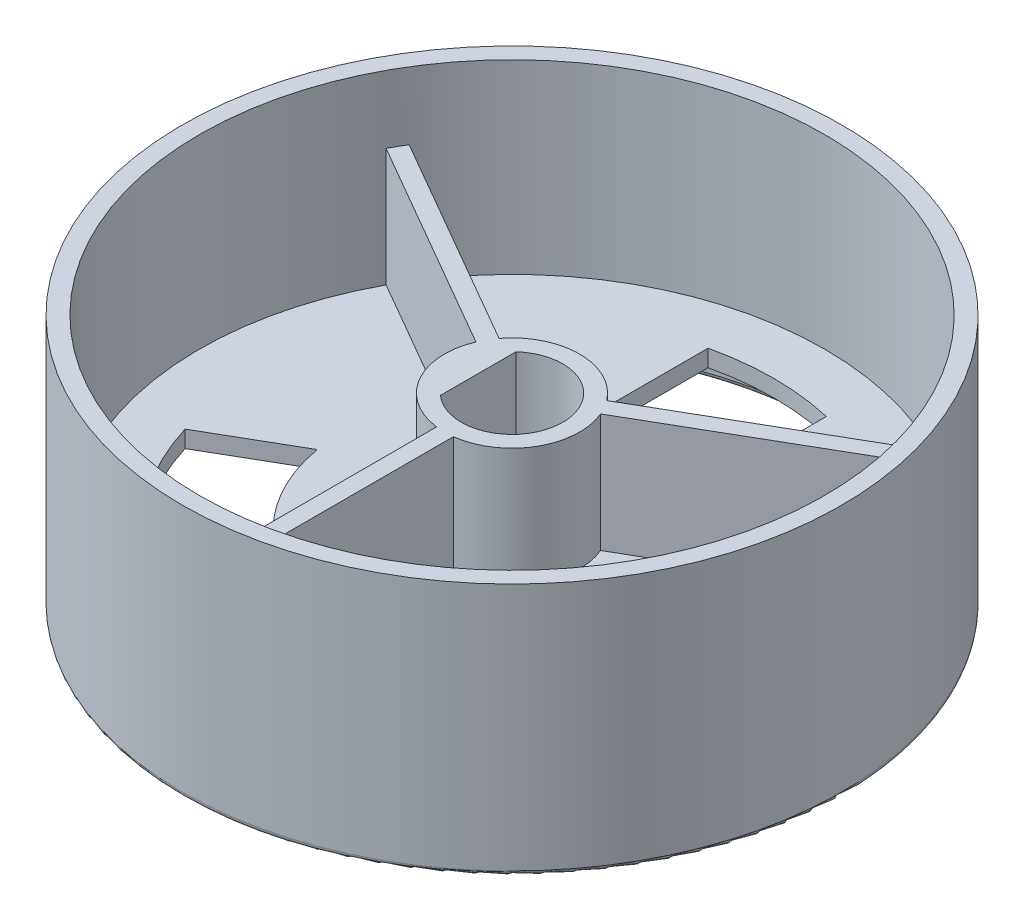
SolidWorks part; units mm, degrees
ref_plane "Front Plane" through (0, 0, 0) normal (0, 0, 1) x (1, 0, 0)
ref_plane "Top Plane" through (0, 0, 0) normal (0, 1, 0) x (1, 0, 0)
ref_plane "Right Plane" through (0, 0, 0) normal (1, 0, 0) x (0, 0, -1)
sketch "Sketch1" plane through (0, 0, 0) normal (0, 1, 0) x (1, 0, 0)
  circle A0 centre (0, 0) radius 18.5
  circle A1 centre (0, 0) radius 19.5
  dimension "D1" = 37
  dimension "D2" = 1
extrude "Boss-Extrude1" add sketch "Sketch1" along normal blind 15
sketch "Sketch2" plane through (0, 0, 0) normal (0, 1, 0) x (1, 0, 0)
  circle A0 centre (0, 0) radius 18.5
  dimension "D1" = 37
extrude "Boss-Extrude2" add sketch "Sketch2" along normal blind 4
sketch "Sketch3" plane through (0, 0, 0) normal (0, -1, 0) x (-1, 0, 0)
  line L0 (0, 0) -> (0, -18.5) construction
  circle A0 centre (0, 0) radius 18.5
  dimension "D1" = 37
extrude "Cut-Extrude1" cut sketch "Sketch3" against normal blind 3
sketch "Sketch6" plane through (0, 3, 0) normal (0, -1, 0) x (-1, 0, 0)
  line L0 (0, 0) -> (0, 20.4551) construction
  line L1 (3.4342, 9.3918) -> (3.5, 9.3918)
  line L3 (-3.5, 15.0997) -> (-3.5, 9.3918)
  line L4 (-3.5, 9.3918) -> (-3.4342, 9.3918)
  line L5 (3.5, 15.0997) -> (3.5, 9.3918)
  circle A0 centre (0, 0) radius 3
  circle A1 centre (0, 0) radius 15.5
  circle A2 centre (0, 0) radius 18.5 construction
  circle A3 centre (0, 0) radius 10
  dimension "D1" = 6
  dimension "D2" = 3
  dimension "D3" = 7
  dimension "D4" = 3.5
  dimension "D5" = 3.5
extrude "Cut-Extrude2" cut sketch "Sketch6" against normal blind 3 contours A3 L0 A1 L3 L4 | L0 A3 L1 L5 A1 region at (1.7619, 3, -12.5778) region at (-1.7619, 3, -12.5778)
pattern_circular "CirPattern1" count 3 over 360 about axis through (0, 0, 0) along (0, 1, 0) of "Cut-Extrude2"
sketch "Sketch8" plane through (0, 3, 0) normal (0, -1, 0) x (1, 0, 0)
  line L0 (-2, 2.2361) -> (-2, -2.2361)
  circle A0 centre (0, 0) radius 3
  circle A1 centre (0, 0) radius 4
  dimension "D1" = 6
  dimension "D2" = 1
  dimension "D3" = 2
extrude "Boss-Extrude28" add sketch "Sketch8" against normal blind 8 contours L0 A0 | A1 A0 region at (-2.4063, 3, 0) region at (-3.8869, 3, 0)
extrude "Cut-Extrude3" cut sketch "Sketch8<3>" against normal blind 8 contours L0 A0 region at (0.296, 3, 0)
sketch "Sketch8<3>" plane through (0, 3, 0) normal (0, -1, 0) x (1, 0, 0) same geometry as "Sketch8"
sketch "Sketch11" plane through (0, 11, 0) normal (0, 1, 0) x (1, 0, 0)
  line L0 (0, -4) -> (0, -18.5) construction
  line L2 (-0.5, -18.8705) -> (0.5, -18.8705)
  line L3 (-0.5, -18.8705) -> (-0.5, -3.6295)
  line L4 (-0.5, -3.6295) -> (0.5, -3.6295)
  line L5 (0.5, -18.8705) -> (0.5, -3.6295)
  line L6 (-0.5, -18.8705) -> (0.5, -3.6295) construction
  line L7 (-0.5, -3.6295) -> (0.5, -18.8705) construction
  circle A0 centre (0, 0) radius 4 construction
  circle A1 centre (0, 0) radius 18.5 construction
  point P7 (0, -11.25)
  dimension "D1" = 1
extrude "Boss-Extrude29" add sketch "Sketch11" against normal blind 8
pattern_circular "CirPattern5" count 3 over 360 about axis through (0, 15, 0) along (0, 1, 0) of "Boss-Extrude29"
sketch "Sketch12" plane through (0, 0, 0) normal (0, -1, 0) x (1, 0, 0)
  line L0 (0, 3) -> (0, 18.5) construction
  line L2 (-0.5, 12.5) -> (0.5, 12.5)
  line L3 (-0.5, 12.5) -> (-0.5, 18.7244)
  line L4 (-0.5, 18.7244) -> (0.5, 18.7244)
  line L5 (0.5, 12.5) -> (0.5, 18.7244)
  arc A0 (-2, -2.2361) -> (-2, 2.2361) centre (0, 0) ccw construction
  circle A1 centre (0, 0) radius 18.5 construction
  point P12 (0, 12.5)
  dimension "D1" = 0.5
  dimension "D2" = 0.5
  dimension "D3" = 9.5
extrude "Boss-Extrude30" add sketch "Sketch12" against normal blind 8
fillet "Fillet7" radius 0.5 2 edges at (-0.5, 1.5, 12.5) (0.5, 1.5, 12.5)
fillet "Fillet8" radius 0.3 6 edges at (0, 0, 19.5) (0, 0, -18.5) (0.5, 0, 15.7466) (0.3536, 0, 12.6464) (-0.3536, 0, 12.6464) (-0.5, 0, 15.7466)
